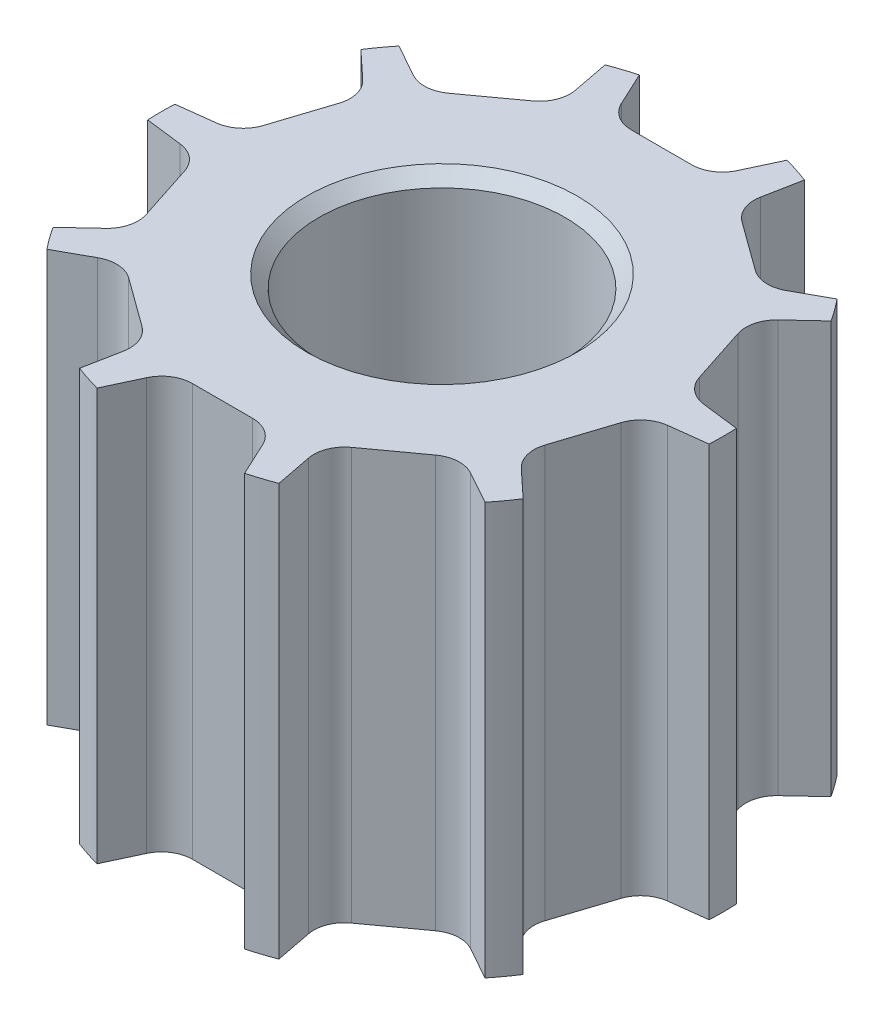
SolidWorks part; units mm, degrees
material "6061-T6 (SS)"
ref_plane "Ebene vorne" through (0, 0, 0) normal (0, 0, 1) x (1, 0, 0)
ref_plane "Ebene oben" through (0, 0, 0) normal (0, 1, 0) x (1, 0, 0)
ref_plane "Ebene rechts" through (0, 0, 0) normal (1, 0, 0) x (0, 0, -1)
ref_axis "Achse1" through (0, -12.75, 0) along (0, 1, 0)
sketch "Skizze1" plane through (0, 0, 0) normal (0, 1, 0) x (1, 0, 0)
  circle A0 centre (0, 0) radius 4.57
  circle A1 centre (0, 0) radius 2
  dimension "D1" = 9.14
  dimension "D2" = 4
extrude "Aufsatz-Linear austragen1" add sketch "Skizze1" along normal blind 6.7
sketch "Skizze12" plane through (0, 6.7, 0) normal (0, 1, 0) x (1, 0, 0)
  line L0 (0, 9.2022) -> (0, -8.7185) construction
  line L1 (-8.4713, 0) -> (7.9602, 0) construction
  line L2 (-1.2, 4.4096) -> (-0.8085, 3.57)
  line L3 (1.2, 4.4096) -> (0.8085, 3.57)
  line L4 (-2.8195, 3.57) -> (2.5735, 3.57) construction
  line L5 (-2.9704, 4.57) -> (2.868, 4.57) construction
  line L6 (-0.8085, 3.57) -> (0.8085, 3.57)
  circle A1 centre (0, 0) radius 4.57 construction
  circle A2 centre (0, 0) radius 4.57 construction
  arc A4 (-1.2, 4.4096) -> (1.2, 4.4096) centre (0, 0) cw
  point P12 (0.8169, 3.57)
  point P14 (0, 0)
  dimension "D1" = 1
  dimension "D5" = 1.6169
  dimension "D6" = 9.14
  dimension "D2" = 2.4
  dimension "D3" = 50
  dimension "D4" = 3.57
extrude "Schnitt-Linear austragen1" cut sketch "Skizze12" against normal through all
fillet "Verrundung1" radius 0.5 2 edges at (0.8085, 3.35, -3.57) (-0.8085, 3.35, -3.57)
pattern_circular "Kreismuster1" count 10 over 360 about axis through (0, -12.75, 0) along (0, 1, 0) of "Schnitt-Linear austragen1", "Verrundung1"
chamfer "Fase2" distance 0.2 angle 45 2 edges at (0, 6.7, 2) (0, 0, 2)
